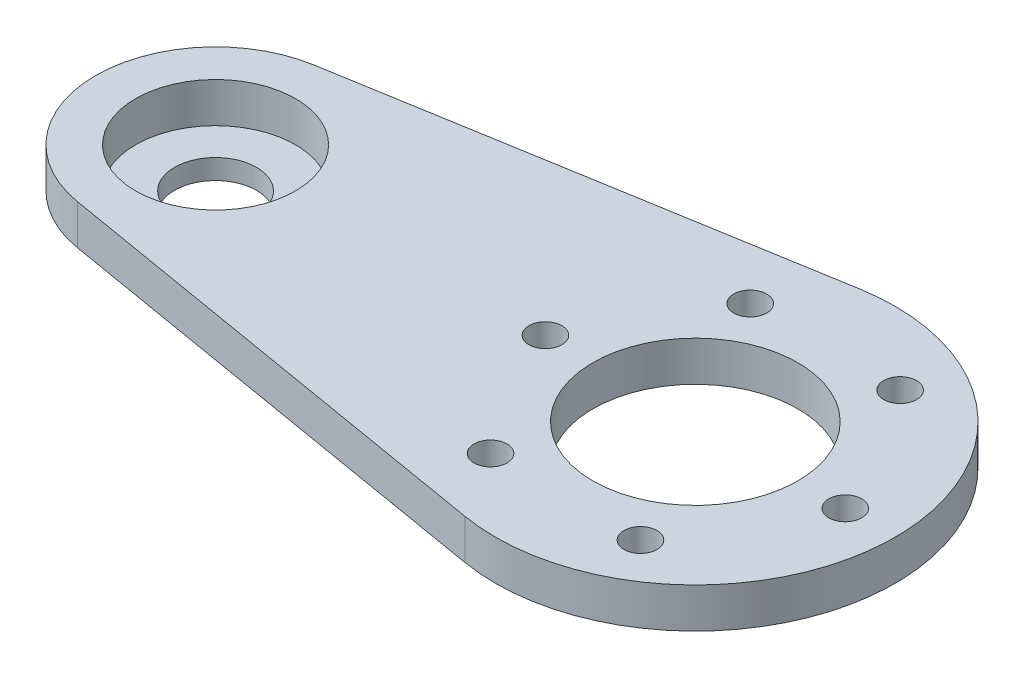
SolidWorks part; units mm, degrees
ref_plane "Front Plane" through (0, 0, 0) normal (0, 0, 1) x (1, 0, 0)
ref_plane "Top Plane" through (0, 0, 0) normal (0, 1, 0) x (1, 0, 0)
ref_plane "Right Plane" through (0, 0, 0) normal (1, 0, 0) x (0, 0, -1)
sketch "Sketch1" plane through (0, 0, 0) normal (0, 1, 0) x (1, 0, 0)
  line L0 (0, 0) -> (-48, 0)
  line L1 (-50, 11.8322) -> (-3.3333, 19.7203)
  line L2 (-50, -11.8322) -> (-3.3333, -19.7203)
  circle A0 centre (0, 0) radius 15 construction
  circle A1 centre (0, 0) radius 10.25
  circle A4 centre (-15, 0) radius 1.65
  circle A5 centre (0, 0) radius 20
  circle A6 centre (-48, 0) radius 4.15
  circle A7 centre (-48, 0) radius 8
  circle A8 centre (-48, 0) radius 12
  circle A11 centre (-7.5, 12.9904) radius 1.65
  circle A12 centre (7.5, 12.9904) radius 1.65
  circle A13 centre (15, 0) radius 1.65
  circle A14 centre (7.5, -12.9904) radius 1.65
  circle A15 centre (-7.5, -12.9904) radius 1.65
  point P21 (0, 0)
  point P29 (0, 0)
  dimension "D1" = 30
  dimension "D2" = 20.5
  dimension "D3" = 3.3
  dimension "D4" = 40
  dimension "D6" = 8.3
  dimension "D7" = 16
  dimension "D8" = 24
  dimension "D5" = 48
  dimension "D9" = 6
extrude "Boss-Extrude1" add sketch "Sketch1" along normal blind 4 contours A8 L0 A5 L1 | A8 L2 A5 L0 | A8 A7 | A5 A4 A1 region at (-27.378, 0, -9.1156) region at (-40.4731, 0, 8.9059) region at (-27.378, 0, 9.1156) region at (-14.8432, 0, -12.5448)
sketch "Sketch4" plane through (0, 0, 0) normal (0, -1, 0) x (1, 0, 0)
  circle A0 centre (-48, 0) radius 8
  circle A1 centre (-48, 0) radius 4.15
  dimension "D1" = 16
  dimension "D2" = 8.3
extrude "Boss-Extrude3" add sketch "Sketch4" along normal blind 2 separate body
sketch "Sketch5" plane through (0, 0, 0) normal (0, -1, 0) x (1, 0, 0)
  circle A0 centre (-48, 0) radius 10
  circle A1 centre (-48, 0) radius 4.1
  dimension "D1" = 20
extrude "Boss-Extrude4" add sketch "Sketch5" along normal up to surface (2 mm away) up to face at (-48, -2, -8)
fillet "Fillet6" radius 2 1 edges at (-48, 0, 10)
